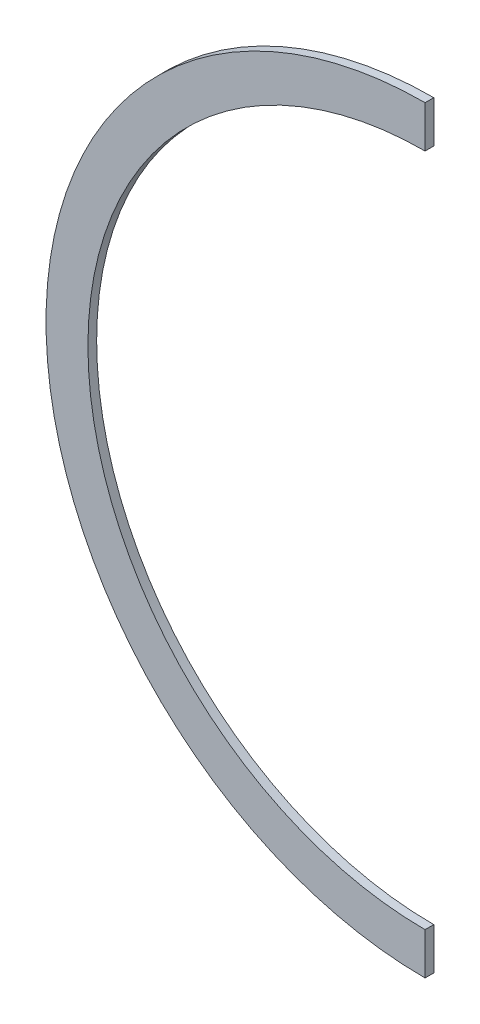
SolidWorks part; units mm, degrees
material "Balsa"
ref_plane "Front Plane" through (0, 0, 0) normal (0, 0, 1) x (1, 0, 0)
ref_plane "Top Plane" through (0, 0, 0) normal (0, 1, 0) x (1, 0, 0)
ref_plane "Right Plane" through (0, 0, 0) normal (1, 0, 0) x (0, 0, -1)
sketch "Sketch1" plane through (0, 0, 0) normal (0, 0, 1) x (1, 0, 0)
  line L0 (0, 0) -> (0, 499.9473) construction
  line L1 (0, -114.7984) -> (0, -129.4545) construction
  line L2 (0, -374.4718) -> (0, 404.2655) construction
  line L3 (-1.651, 142.9921) -> (-1.651, 150.6121) construction
  line L4 (1.651, 142.9921) -> (1.651, 150.6121) construction
  line L5 (-1.651, 142.9921) -> (1.651, 142.9921) construction
  line L6 (136.2041, -53.806) -> (0.0002, 24.7625) construction
  line L7 (-136.2076, -53.7991) -> (0.0002, 24.7625) construction
  line L8 (136.2041, -53.806) -> (0.0002, 24.7625) construction
  line L9 (-136.2076, -53.7991) -> (0.0002, 24.7625) construction
  line L10 (-125.0584, -45.4626) -> (-118.4576, -41.6554) construction
  line L11 (-123.6259, -48.4483) -> (-116.8078, -44.5157) construction
  line L12 (-118.4576, -41.6554) -> (-116.8078, -44.5157) construction
  line L13 (-124.1455, -48.7479) -> (-123.6847, -48.4822) construction
  line L14 (-123.6847, -48.4822) -> (-123.6259, -48.4483) construction
  line L15 (-125.7952, -45.8876) -> (-125.1113, -45.4931) construction
  line L16 (-125.1113, -45.4931) -> (-125.0584, -45.4626) construction
  line L17 (125.4797, -45.7137) -> (125.1075, -45.499) construction
  line L18 (123.8298, -48.5739) -> (123.6807, -48.488) construction
  line L19 (117.0223, -44.647) -> (118.6722, -41.7868) construction
  line L20 (123.6807, -48.488) -> (123.6228, -48.4545) construction
  line L21 (123.6228, -48.4545) -> (117.0223, -44.647) construction
  line L22 (125.1075, -45.499) -> (125.0554, -45.4689) construction
  line L23 (125.0554, -45.4689) -> (118.6722, -41.7868) construction
  line L24 (-107.079, -46.8884) -> (-120.3798, -54.5735)
  line L25 (-108.6638, -44.1348) -> (-121.9647, -51.8199)
  line L28 (-115.4206, -47.9666) -> (-121.9445, -51.7361) construction
  line L29 (-120.2754, -54.5131) -> (-108.646, -44.1245) construction
  line L30 (-114.4607, -49.3188) -> (-122.1124, -53.7399) construction
  line L31 (-113.7686, -50.8257) -> (-120.3665, -54.6379) construction
  line L32 (-115.4206, -47.9666) -> (-113.7686, -50.8257) construction
  line L33 (106.3137, -46.4532) -> (129.9098, -60.0883)
  line L34 (107.9004, -43.7007) -> (131.505, -57.3407)
  line L35 (129.9098, -60.0883) -> (131.505, -57.3407)
  line L36 (129.9098, -60.0883) -> (131.505, -57.3407) construction
  line L37 (107.9004, -43.7007) -> (131.505, -57.3407) construction
  line L38 (106.3137, -46.4532) -> (129.9098, -60.0883) construction
  line L39 (129.9098, -60.0883) -> (107.9004, -43.7007) construction
  line L40 (118.9051, -51.8945) -> (101.8722, -42.0519) construction
  line L41 (120.3631, -54.6438) -> (113.7655, -50.8313)
  line L42 (122.0152, -51.7848) -> (122.0057, -51.7794) construction
  line L43 (113.7655, -50.8313) -> (115.4176, -47.9723)
  line L44 (122.0057, -51.7794) -> (121.9413, -51.7421) construction
  line L45 (121.9413, -51.7421) -> (115.4176, -47.9723)
  line L46 (-108.6638, -44.1348) -> (-121.9647, -51.8199)
  line L47 (-107.079, -46.8884) -> (-120.3798, -54.5735)
  arc A0 (-1.651, 150.6121) -> (-125.0584, -45.4626) centre (0, 12.7) ccw
  circle A1 centre (0, 12.7) radius 120.904
  arc A2 (0, 150.622) -> (-1.651, 150.6121) centre (0, 12.7) ccw
  circle A3 centre (0, 12.7) radius 137.922 construction
  arc A4 (1.651, 150.6121) -> (0, 150.622) centre (0, 12.7) ccw
  arc A5 (-124.3508, -46.9604) -> (-123.6259, -48.4483) centre (0, 12.7) ccw
  arc A6 (-123.6259, -48.4483) -> (-121.9445, -51.7361) centre (0, 12.7) ccw
  arc A7 (-125.0584, -45.4626) -> (-124.3508, -46.9604) centre (0, 12.7) ccw
  arc A8 (124.3477, -46.9667) -> (125.0554, -45.4689) centre (0, 12.7) ccw
  arc A9 (125.0554, -45.4689) -> (1.651, 150.6121) centre (0, 12.7) ccw
  arc A10 (123.6228, -48.4545) -> (124.3477, -46.9667) centre (0, 12.7) ccw
  arc A11 (-121.9153, -51.7914) -> (-121.1641, -53.1919) centre (0, 12.7) ccw
  arc A12 (-120.3665, -54.6379) -> (120.3631, -54.6438) centre (0, 12.7) ccw
  arc A13 (-121.9445, -51.7361) -> (-121.9153, -51.7914) centre (0, 12.7) ccw
  arc A14 (-121.1641, -53.1919) -> (-120.3827, -54.6089) centre (0, 12.7) ccw
  arc A15 (-120.3827, -54.6089) -> (-120.397, -54.5834) centre (0, 12.7) ccw construction
  arc A16 (-120.397, -54.5834) -> (-120.3665, -54.6379) centre (0, 12.7) ccw construction
  arc A17 (120.3936, -54.5893) -> (121.0149, -53.4654) centre (0, 12.7) ccw construction
  arc A18 (121.9413, -51.7421) -> (123.6228, -48.4545) centre (0, 12.7) ccw
  arc A19 (120.3631, -54.6438) -> (120.3936, -54.5893) centre (0, 12.7) ccw construction
  arc A20 (121.0149, -53.4654) -> (121.9121, -51.7974) centre (0, 12.7) ccw construction
  arc A21 (121.9121, -51.7974) -> (121.9413, -51.7421) centre (0, 12.7) ccw construction
  spline S0 degree 3 poles (106.3137, -46.4532) (106.8426, -45.5357) (107.3715, -44.6182) (107.9004, -43.7007) knots 0 0 0 0 1 1 1 1 weights 1 1 1 1
  spline S1 degree 3 poles (-66.0123, 133.6164) (-70.0128, 131.4329) (-73.8716, 129.0699) (-81.3156, 123.9975) (-84.9009, 121.288) (-91.7995, 115.5249) (-95.113, 112.4712) (-99.0811, 108.4341) (-99.866, 107.6157) (-101.4182, 105.9565) (-102.1865, 105.1147) (-104.4569, 102.5643) (-105.9223, 100.8334) (-110.1768, 95.5512) (-115.4725, 88.2691) (-120.0285, 80.5179) (-123.1654, 74.5269) (-124.1643, 72.5002) (-125.5914, 69.415) (-126.0551, 68.3791) (-126.9587, 66.292) (-127.3989, 65.2397) (-129.5278, 59.9684) (-131.0098, 55.7) (-133.5456, 47.0638) (-134.5993, 42.696) (-136.2795, 33.8613) (-136.906, 29.3944) (-137.415, 23.7472) (-137.5031, 22.6146) (-137.6514, 20.3429) (-137.7116, 19.2049) (-137.8496, 15.7999) (-137.8852, 13.5361) (-137.8263, 6.7629) (-137.3062, -2.2197) (-135.9163, -11.1068) (-134.5433, -17.7359) (-134.0304, -19.9395) (-132.8922, -24.3345) (-132.2653, -26.5303) (-130.2347, -33.03) (-128.6774, -37.2656) (-126.1245, -43.2881) (-125.286, -45.1501) (-124.4066, -46.9926) knots 0 0 0 0 0.03125 0.03125 0.0625 0.0625 0.09375 0.09375 0.101563 0.101563 0.109375 0.109375 0.125 0.125 0.15625 0.1875 0.1875 0.203125 0.203125 0.210938 0.210938 0.21875 0.21875 0.25 0.25 0.28125 0.28125 0.3125 0.3125 0.320313 0.320313 0.328125 0.328125 0.34375 0.34375 0.375 0.40625 0.40625 0.421875 0.421875 0.4375 0.4375 0.46875 0.46875 0.48295 0.48295 0.48295 0.48295 construction
  spline S2 degree 3 poles (-2953.7904, 2461.9899) (-820.777, 189.8449) (-138.9507, -249.535) (81.4542, -98.9353) (85.033, -96.2237) (91.9188, -90.4573) (95.2258, -87.4025) (99.1858, -83.3647) (99.9691, -82.5461) (101.5182, -80.8868) (102.2849, -80.0449) (104.5506, -77.4941) (106.013, -75.7632) (110.2586, -70.4809) (112.9006, -66.8403) (117.8152, -59.3254) (120.0877, -55.4512) (123.2166, -49.4629) (124.2129, -47.4373) (125.6361, -44.3538) (126.0986, -43.3185) (126.9997, -41.2327) (127.4386, -40.181) (129.5618, -34.9121) (131.0396, -30.646) (133.5674, -22.0152) (134.6173, -17.6505) (136.2906, -8.8227) (136.914, -4.3596) (137.4197, 1.2823) (137.5071, 2.4139) (137.6542, 4.6834) (137.7138, 5.8206) (137.85, 9.2232) (137.8846, 11.4853) (137.8228, 18.2533) (137.2995, 27.2283) (135.9081, 36.1069) (134.5347, 42.7292) (134.0218, 44.9305) (132.8839, 49.3207) (132.2571, 51.5145) (130.2267, 58.0093) (128.67, 62.2416) (125.1615, 70.5162) (123.2097, 74.5586) (118.9108, 82.4534) (116.5637, 86.3058) (113.3753, 90.999) (112.7241, 91.9325) (111.3996, 93.7822) (110.7272, 94.697) (108.6802, 97.4113) (107.2757, 99.181) (102.9447, 104.3725) (96.8571, 110.9816) (90.1513, 116.9722) (84.8861, 121.2292) (83.0917, 122.6088) (80.3399, 124.6181) (79.4113, 125.2786) (77.543, 126.5731) (76.6028, 127.2075) (71.8708, 130.3161) (67.9881, 132.6004) (60.0328, 136.7739) (55.9603, 138.6631) (47.6249, 142.0446) (43.3619, 143.537) (37.9102, 145.1462) (36.8136, 145.4551) (34.6205, 146.0438) (33.5224, 146.3241) (30.2234, 147.1229) (28.0179, 147.5997) (21.3832, 148.8649) (16.9358, 149.4889) (7.993, 150.3014) (3.4975, 150.4899) (-3.2824, 150.4396) (-5.5486, 150.3672) (-10.0934, 150.1088) (-12.3559, 149.9236) (-19.101, 149.2046) (-23.5473, 148.5072) (-32.3412, 146.6856) (-36.6887, 145.5614) (-43.1354, 143.5526) (-45.2718, 142.8291) (-49.5193, 141.273) (-51.6323, 140.4395) (-369.2659, 5.9249) (-132.0865, -1278.1783) (677.8124, -3754.3927) knots -1.791229 -1.791229 -1.791229 -1.791229 0.03125 0.03125 0.0625 0.0625 0.09375 0.09375 0.101563 0.101563 0.109375 0.109375 0.125 0.125 0.15625 0.15625 0.1875 0.1875 0.203125 0.203125 0.210938 0.210938 0.21875 0.21875 0.25 0.25 0.28125 0.28125 0.3125 0.3125 0.320313 0.320313 0.328125 0.328125 0.34375 0.34375 0.375 0.40625 0.40625 0.421875 0.421875 0.4375 0.4375 0.46875 0.46875 0.5 0.5 0.53125 0.53125 0.539062 0.539062 0.546875 0.546875 0.5625 0.5625 0.59375 0.625 0.625 0.640625 0.640625 0.648437 0.648437 0.65625 0.65625 0.6875 0.6875 0.71875 0.71875 0.75 0.75 0.757812 0.757812 0.765625 0.765625 0.78125 0.78125 0.8125 0.8125 0.84375 0.84375 0.859375 0.859375 0.875 0.875 0.90625 0.90625 0.9375 0.9375 0.953125 0.953125 0.96875 0.96875 3.320852 3.320852 3.320852 3.320852 only from (66.1767, -108.566) to (-66.0123, 133.6164)
  spline S3 degree 3 poles (66.1767, -108.566) (70.1708, -106.3789) (74.0231, -104.0129) (81.4542, -98.9353) (85.033, -96.2237) (91.9188, -90.4573) (95.2258, -87.4025) (99.1858, -83.3647) (99.9691, -82.5461) (101.5182, -80.8868) (102.2849, -80.0449) (104.5506, -77.4941) (106.013, -75.7632) (110.2586, -70.4809) (112.9006, -66.8403) (117.8152, -59.3254) (120.0877, -55.4512) (123.2166, -49.4629) (124.2129, -47.4373) (125.6361, -44.3538) (126.0986, -43.3185) (126.9997, -41.2327) (127.4386, -40.181) (129.5618, -34.9121) (131.0396, -30.646) (133.5674, -22.0152) (134.6173, -17.6505) (136.2906, -8.8227) (136.914, -4.3596) (137.4197, 1.2823) (137.5071, 2.4139) (137.6542, 4.6834) (137.7138, 5.8206) (137.85, 9.2232) (137.8846, 11.4853) (137.8228, 18.2533) (137.2995, 27.2283) (135.9081, 36.1069) (134.5347, 42.7292) (134.0218, 44.9305) (132.8839, 49.3207) (132.2571, 51.5145) (130.2267, 58.0093) (128.67, 62.2416) (125.1615, 70.5162) (123.2097, 74.5586) (118.9108, 82.4534) (116.5637, 86.3058) (113.3753, 90.999) (112.7241, 91.9325) (111.3996, 93.7822) (110.7272, 94.697) (108.6802, 97.4113) (107.2757, 99.181) (102.9447, 104.3725) (96.8571, 110.9816) (90.1513, 116.9722) (84.8861, 121.2292) (83.0917, 122.6088) (80.3399, 124.6181) (79.4113, 125.2786) (77.543, 126.5731) (76.6028, 127.2075) (71.8708, 130.3161) (67.9881, 132.6004) (60.0328, 136.7739) (55.9603, 138.6631) (47.6249, 142.0446) (43.3619, 143.537) (37.9102, 145.1462) (36.8136, 145.4551) (34.6205, 146.0438) (33.5224, 146.3241) (30.2234, 147.1229) (28.0179, 147.5997) (21.3832, 148.8649) (16.9358, 149.4889) (7.993, 150.3014) (3.4975, 150.4899) (-3.2824, 150.4396) (-5.5486, 150.3672) (-10.0934, 150.1088) (-12.3559, 149.9236) (-19.101, 149.2046) (-23.5473, 148.5072) (-32.3412, 146.6856) (-36.6887, 145.5614) (-43.1354, 143.5526) (-45.2718, 142.8291) (-49.5193, 141.273) (-51.6323, 140.4395) (-57.9206, 137.7764) (-62.0153, 135.798) (-66.0123, 133.6164) knots 0 0 0 0 0.03125 0.03125 0.0625 0.0625 0.09375 0.09375 0.101563 0.101563 0.109375 0.109375 0.125 0.125 0.15625 0.15625 0.1875 0.1875 0.203125 0.203125 0.210938 0.210938 0.21875 0.21875 0.25 0.25 0.28125 0.28125 0.3125 0.3125 0.320313 0.320313 0.328125 0.328125 0.34375 0.34375 0.375 0.40625 0.40625 0.421875 0.421875 0.4375 0.4375 0.46875 0.46875 0.5 0.5 0.53125 0.53125 0.539062 0.539062 0.546875 0.546875 0.5625 0.5625 0.59375 0.625 0.625 0.640625 0.640625 0.648437 0.648437 0.65625 0.65625 0.6875 0.6875 0.71875 0.71875 0.75 0.75 0.757812 0.757812 0.765625 0.765625 0.78125 0.78125 0.8125 0.8125 0.84375 0.84375 0.859375 0.859375 0.875 0.875 0.90625 0.90625 0.9375 0.9375 0.953125 0.953125 0.96875 0.96875 1 1 1 1 construction
  spline S4 degree 3 poles (-124.4066, -46.9926) (-124.169, -47.4906) (-123.9283, -47.9871) (-123.6847, -48.4822) knots 0.48295 0.48295 0.48295 0.48295 0.486788 0.486788 0.486788 0.486788 construction
  spline S5 degree 3 poles (-123.6847, -48.4822) (-122.846, -50.1865) (-121.9718, -51.874) (-118.9108, -57.4955) (-116.5612, -61.3517) (-113.369, -66.0497) (-112.7169, -66.9844) (-111.3913, -68.8351) (-110.7184, -69.7503) (-108.6697, -72.4662) (-107.264, -74.2369) (-102.929, -79.4315) (-96.8353, -86.0447) (-90.1214, -92.0392) (-84.8493, -96.299) (-83.0524, -97.6795) (-80.2967, -99.6899) (-79.367, -100.3507) (-77.4971, -101.6451) (-76.5559, -102.2795) (-71.8198, -105.3881) (-67.9332, -107.6723) (-59.9695, -111.8452) (-55.8924, -113.7339) (-47.5468, -117.114) (-43.2782, -118.6053) (-37.8188, -120.2127) (-36.7216, -120.521) (-34.5268, -121.1085) (-33.4279, -121.3881) (-30.1264, -122.185) (-27.9191, -122.6605) (-21.2788, -123.9216) (-16.8274, -124.5426) (-7.8757, -125.3484) (-3.3755, -125.5332) (3.4122, -125.4766) (5.6812, -125.4019) (10.231, -125.1387) (12.493, -124.9512) (19.2413, -124.2249) (23.6899, -123.5224) (32.4889, -121.6898) (36.8393, -120.5597) (43.2904, -118.5412) (45.4283, -117.8143) (48.6163, -116.6419) (49.6759, -116.2374) (51.7885, -115.4006) (52.8426, -114.968) (58.0839, -112.7404) (62.1792, -110.755) (66.1767, -108.566) knots 0.486788 0.486788 0.486788 0.486788 0.5 0.5 0.53125 0.53125 0.539062 0.539062 0.546875 0.546875 0.5625 0.5625 0.59375 0.625 0.625 0.640625 0.640625 0.648437 0.648437 0.65625 0.65625 0.6875 0.6875 0.71875 0.71875 0.75 0.75 0.757812 0.757812 0.765625 0.765625 0.78125 0.78125 0.8125 0.8125 0.84375 0.84375 0.859375 0.859375 0.875 0.875 0.90625 0.90625 0.9375 0.9375 0.953125 0.953125 0.960937 0.960937 0.96875 0.96875 1 1 1 1 construction
  spline S6 degree 3 poles (-108.6638, -44.1348) (-108.1355, -45.0527) (-107.6073, -45.9705) (-107.079, -46.8884) knots 0 0 0 0 1 1 1 1 weights 1 1 1 1
  spline S7 degree 3 poles (-121.9647, -51.8199) (-121.4364, -52.7377) (-120.9081, -53.6556) (-120.3798, -54.5735) knots 0 0 0 0 1 1 1 1 weights 1 1 1 1
  spline S8 degree 3 poles (-1893.2868, -3504.9508) (-555.1038, -1197.2913) (777.7443, 1114.8675) (2098.5226, 3419.8495) knots -1257.715582 -1257.715582 -1257.715582 -1257.715582 1261.2826 1261.2826 1261.2826 1261.2826 weights 1.001261 0.999578 0.99958 1.001266 only from (106.3137, -46.4532) to (107.9004, -43.7007)
  spline S9 degree 3 poles (-121.8597, -51.7592) (-121.5948, -52.2177) (-121.3299, -52.6762) (-121.065, -53.1347) knots 0 0 0 0 0.5 0.5 0.5 0.5 weights 1 1 1 1 construction
  spline S12 degree 3 poles (-2107.5184, 3411.1282) (-794.411, 1112.1626) (537.2029, -1201.4874) (1876.5356, -3511.0638) knots -1261.624621 -1261.624621 -1261.624621 -1261.624621 1257.384167 1257.384167 1257.384167 1257.384167 weights 1.00204 0.999326 0.99932 1.002023 only from (-121.9647, -51.8199) to (-120.3798, -54.5735)
  spline S13 degree 3 poles (-2094.7969, 3419.3607) (-780.7303, 1119.4679) (550.7427, -1194.0569) (1889.8709, -3504.2883) knots -1261.518414 -1261.518414 -1261.518414 -1261.518414 1257.484402 1257.484402 1257.484402 1257.484402 weights 1.00184 0.999392 0.999387 1.001825 only from (-108.6638, -44.1348) to (-107.079, -46.8884)
  point P7 (0, -125.5003)
  point P8 (0, 150.4602)
  point P25 (-125.0584, -45.4626)
  point P38 (123.6228, -48.4545)
  dimension "D2" = 275.844
  dimension "D1" = 275.9605
  dimension "D3" = 12.7
  dimension "D5" = 3.302
  dimension "D6" = 7.62
  dimension "D7" = 3.302
  dimension "D8" = 7.62
  dimension "D9" = 3.302
  dimension "D10" = 7.62
  dimension "D11" = 3.302
  dimension "D12" = 7.62
  dimension "D13" = 3.302
  dimension "D14" = 7.62
  dimension "D4" = 17.018
extrude "Boss-Extrude1" [suppressed] add sketch "Sketch1" along normal mid plane 3.175
sketch "Sketch2" plane through (248.2736, -245.0135, 0) normal (0, 0, -1) x (0, -1, 0)
  line L3 (-245.0135, 248.2736) -> (-427.6569, 248.2736) construction
  circle A1 centre (-257.7135, 248.2736) radius 137.922
  circle A16 centre (-257.7135, 248.2736) radius 122.682
  dimension "D1" = 12.7
  dimension "D2" = 275.844
  dimension "D3" = 15.24
fillet "Fillet1" [suppressed] radius 1.27
extrude "Boss-Extrude2" add sketch "Sketch2" along normal mid plane 3.175
sketch "Sketch3" plane through (0, 0, 0) normal (1, 0, 0) x (0, 0, -1)
  line L1 (-141.282, 263.3615) -> (149.6958, 263.3615)
  line L2 (-141.282, 263.3615) -> (-141.282, -241.4673)
  line L3 (-141.282, -241.4673) -> (149.6958, -241.4673)
  line L4 (149.6958, 263.3615) -> (149.6958, -241.4673)
extrude "Cut-Extrude1" cut sketch "Sketch3" along normal through all
equation "\"slotwidth\"=0.13"
equation "\"D11@Sketch1\"=\"slotwidth\""
